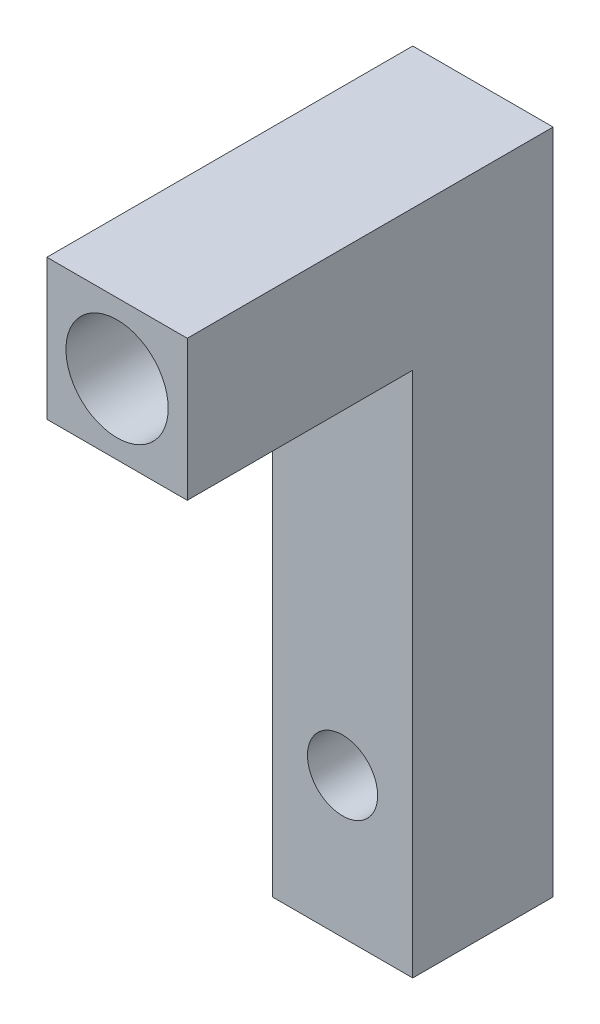
SolidWorks part; units mm, degrees
ref_plane "Front Plane" through (0, 0, 0) normal (0, 0, 1) x (1, 0, 0)
ref_plane "Top Plane" through (0, 0, 0) normal (0, 1, 0) x (1, 0, 0)
ref_plane "Right Plane" through (0, 0, 0) normal (1, 0, 0) x (0, 0, -1)
sketch "Sketch2" plane through (0, 0, 0) normal (0, 1, 0) x (1, 0, 0)
  line L1 (-25.4, -25.4) -> (25.4, -25.4)
  line L2 (-25.4, -25.4) -> (-25.4, 25.4)
  line L3 (-25.4, 25.4) -> (25.4, 25.4)
  line L4 (25.4, -25.4) -> (25.4, 25.4)
  line L5 (-25.4, -25.4) -> (25.4, 25.4) construction
  line L6 (-25.4, 25.4) -> (25.4, -25.4) construction
  point P0 (0, 0)
  dimension "D1" = 50.8
extrude "Boss-Extrude1" add sketch "Sketch2" along normal blind 241.3
sketch "Sketch3" plane through (0, 0, 25.4) normal (0, 0, 1) x (1, 0, 0)
  line L0 (0, 0) -> (0, 38.1) construction
  line L1 (-25.4, 0) -> (25.4, 0) construction
  line L2 (0, 38.1) -> (0, 50.8) construction
  circle A0 centre (0, 50.8) radius 12.7
  dimension "D3" = 25.4
  dimension "D1" = 38.1
  dimension "D2" = 12.7
extrude "Cut-Extrude1" cut sketch "Sketch3" against normal through all
sketch "Sketch4" plane through (0, 241.3, 0) normal (0, 1, 0) x (1, 0, 0)
  line L0 (-25.4, 25.4) -> (-25.4, -107) construction
  line L1 (-25.4, 25.4) -> (-25.4, -25.4) construction
  line L2 (25.4, 25.4) -> (-25.4, 25.4) construction
  line L4 (-25.4, -107) -> (25.4, -107)
  line L5 (-25.4, -107) -> (-25.4, 25.4)
  line L6 (-25.4, 25.4) -> (25.4, 25.4)
  line L7 (25.4, -107) -> (25.4, 25.4)
  line L8 (-25.4, -107) -> (25.4, 25.4) construction
  line L9 (-25.4, 25.4) -> (25.4, -107) construction
  point P9 (0, -40.8)
  dimension "D1" = 132.4
extrude "Boss-Extrude2" add sketch "Sketch4" against normal blind 50.8
sketch "Sketch5" plane through (0, 0, 107) normal (0, 0, 1) x (1, 0, 0)
  line L0 (0, 241.3) -> (0, 215.9) construction
  line L1 (-25.4, 241.3) -> (25.4, 241.3) construction
  circle A0 centre (0, 215.9) radius 18.5
  dimension "D2" = 37
  dimension "D1" = 25.4
extrude "Cut-Extrude2" cut sketch "Sketch5" against normal through all
